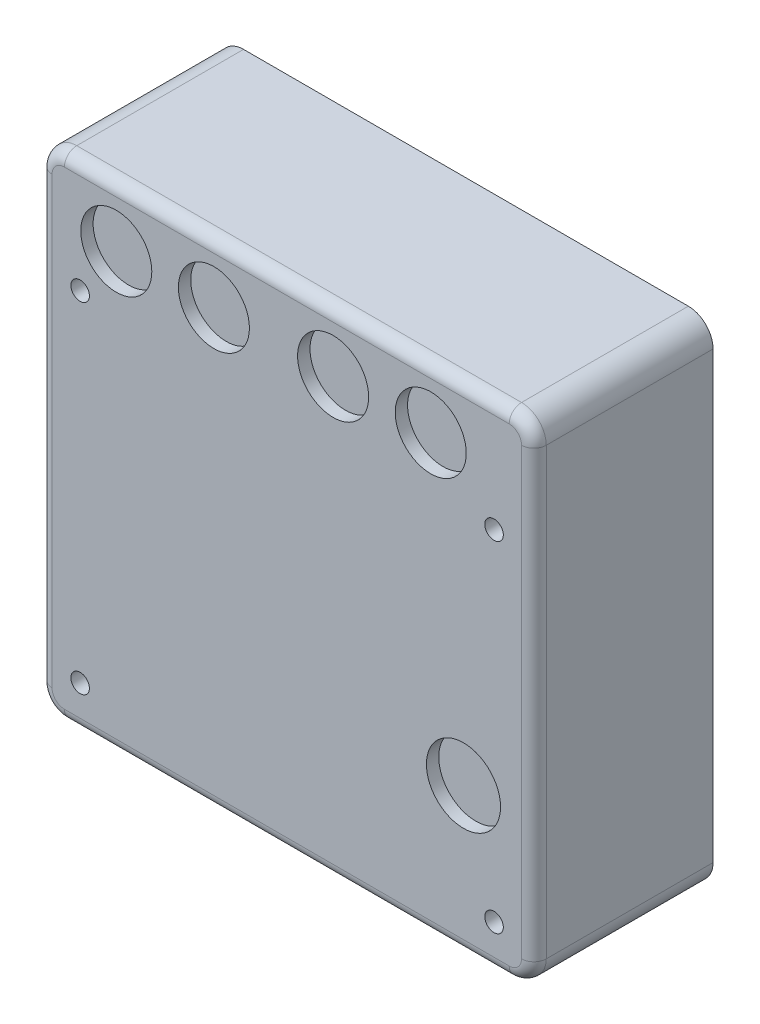
SolidWorks part; units mm, degrees
ref_plane "Front Plane" through (0, 0, 0) normal (0, 0, 1) x (1, 0, 0)
ref_plane "Top Plane" through (0, 0, 0) normal (0, 1, 0) x (1, 0, 0)
ref_plane "Right Plane" through (0, 0, 0) normal (1, 0, 0) x (0, 0, -1)
sketch "Sketch1" plane through (0, 0, 0) normal (0, 0, 1) x (1, 0, 0)
  line L1 (-40, 40) -> (40, 40)
  line L2 (-40, 40) -> (-40, -40)
  line L3 (-40, -40) -> (40, -40)
  line L4 (40, 40) -> (40, -40)
  line L5 (-40, 40) -> (40, -40) construction
  line L6 (-40, -40) -> (40, 40) construction
  point P0 (0, 0)
  dimension "D1" = 80
  dimension "D2" = 80
extrude "Boss-Extrude1" add sketch "Sketch1" along normal mid plane 29
fillet "Fillet1" radius 2 4 edges at (40, 0, 14.5) (0, -40, 14.5) (-40, 0, 14.5) (0, 40, 14.5)
fillet "Fillet2" radius 4 8 edges at (-39.4142, 39.4142, 13.9142) (39.4142, 39.4142, 13.9142) (-39.4142, -39.4142, 13.9142) (39.4142, -39.4142, 13.9142) (40, -40, -1) (-40, -40, -1) (40, 40, -1) (-40, 40, -1)
sketch "Sketch2" plane through (0, 0, 14.5) normal (0, 0, 1) x (1, 0, 0)
  line L0 (-27.6, 30.4) -> (-11.8, 30.4) construction
  line L1 (-11.8, 30.4) -> (7.5, 30.4) construction
  line L2 (7.5, 30.4) -> (23.3, 30.4) construction
  line L3 (-36, 40) -> (36, 40) construction
  line L4 (-40, -36) -> (-40, 36) construction
  circle A0 centre (-27.6, 30.4) radius 5.75
  circle A1 centre (-11.8, 30.4) radius 5.75
  circle A2 centre (7.5, 30.4) radius 5.75
  circle A3 centre (23.3, 30.4) radius 5.75
  dimension "D1" = 11.5
  dimension "D4" = 19.3
  dimension "D5" = 12.4
  dimension "D2" = 9.6
  dimension "D3" = 15.8
extrude "Cut-Extrude1" cut sketch "Sketch2" against normal blind 2
sketch "Sketch3" plane through (0, 0, 14.5) normal (0, 0, 1) x (1, 0, 0)
  line L1 (-33.45, 21.95) -> (33.55, 21.95) construction
  line L2 (-33.45, 21.95) -> (-33.45, -33.05) construction
  line L3 (-33.45, -33.05) -> (33.55, -33.05) construction
  line L4 (33.55, 21.95) -> (33.55, -33.05) construction
  circle A0 centre (-33.45, 21.95) radius 1.5
  circle A2 centre (33.55, 21.95) radius 1.5
  circle A3 centre (-33.45, -33.05) radius 1.5
  circle A4 centre (33.55, -33.05) radius 1.5
  circle A5 centre (23.3, 30.4) radius 5.75 construction
  circle A6 centre (23.3, 30.4) radius 5.75 construction
  dimension "D5" = 3
  dimension "D3" = 10.25
  dimension "D4" = 8.45
  dimension "D1" = 55
  dimension "D2" = 67
extrude "Cut-Extrude2" cut sketch "Sketch3" against normal blind 12
sketch "Sketch6" plane through (0, 0, 14.5) normal (0, 0, 1) x (1, 0, 0)
  circle A0 centre (28.6, -16.4) radius 6
  circle A1 centre (23.3, 30.4) radius 5.75 construction
  circle A2 centre (23.3, 30.4) radius 5.75 construction
  dimension "D1" = 12
  dimension "D2" = 5.3
  dimension "D3" = 46.8
extrude "Cut-Extrude3" cut sketch "Sketch6" against normal blind 2
sketch "Sketch7" plane through (0, 0, -14.5) normal (0, 0, -1) x (-1, 0, 0)
  line L1 (-16.75, 21) -> (16.75, 21)
  line L2 (-16.75, 21) -> (-16.75, -21)
  line L3 (-16.75, -21) -> (16.75, -21)
  line L4 (16.75, 21) -> (16.75, -21)
  line L5 (-16.75, 21) -> (16.75, -21) construction
  line L6 (-16.75, -21) -> (16.75, 21) construction
  point P0 (0, 0)
  dimension "D1" = 42
  dimension "D2" = 33.5
